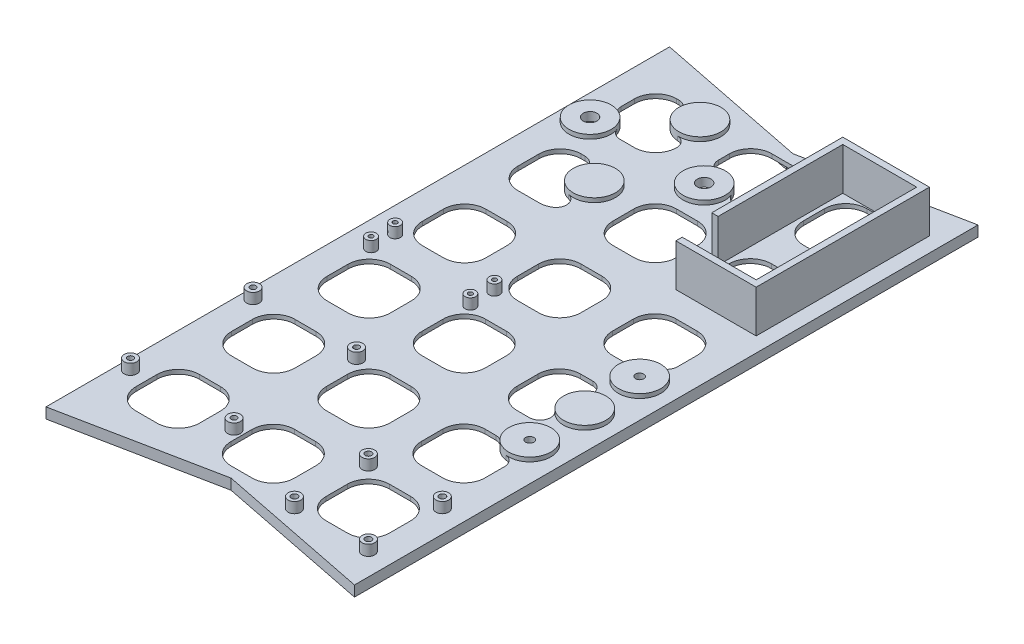
SolidWorks part; units mm, degrees
ref_plane "Front Plane" through (0, 0, 0) normal (0, 0, 1) x (1, 0, 0)
ref_plane "Top Plane" through (0, 0, 0) normal (0, 1, 0) x (1, 0, 0)
ref_plane "Right Plane" through (0, 0, 0) normal (1, 0, 0) x (0, 0, -1)
ref_axis "X" through (-88.99, 0, 0) along (1, 0, 0)
ref_axis "Y" through (0, 55, 0) along (0, -1, 0)
ref_axis "Z" through (0, 0, -88.99) along (0, 0, 1)
sketch "Sketch1" plane through (0, 0, 0) normal (0, 1, 0) x (1, 0, 0)
  line L0 (-75, 150) -> (0, 135) construction
  line L1 (-75, 150) -> (75, 150) construction
  line L2 (-75, 150) -> (-75, -150) construction
  line L3 (-75, -150) -> (75, -150) construction
  line L4 (75, 150) -> (75, -150) construction
  line L5 (-75, 150) -> (75, -150) construction
  line L6 (-75, -150) -> (75, 150) construction
  line L7 (0, 135) -> (75, 150) construction
  line L8 (-75, 0) -> (75, 0) construction
  line L9 (-75, -150) -> (0, -135) construction
  line L10 (0, -135) -> (75, -150) construction
  line L11 (-73, 147.5604) -> (-73, -147.5604)
  line L12 (-73, -147.5604) -> (0, -132.9604)
  line L13 (0, -132.9604) -> (73, -147.5604)
  line L14 (73, 147.5604) -> (73, -147.5604)
  line L15 (0, 132.9604) -> (73, 147.5604)
  line L16 (-73, 147.5604) -> (0, 132.9604)
  point P0 (0, 0)
  dimension "D1" = 300
  dimension "D2" = 150
  dimension "D3" = 15
  dimension "D4" = 2
extrude "Boss-Extrude1" add sketch "Sketch1" along normal blind 2
sketch "Sketch2" plane through (0, 2, 0) normal (0, 1, 0) x (1, 0, 0)
  line L0 (-73, 147.5604) -> (-73, -147.5604) construction
  line L1 (-50, -127.9604) -> (-40, -127.9604)
  line L2 (-60, -117.9604) -> (-60, -107.9604)
  line L3 (-50, -97.9604) -> (-40, -97.9604)
  line L4 (-30, -117.9604) -> (-30, -107.9604)
  line L5 (-15, -117.9604) -> (-15, -107.9604)
  line L6 (-5, -127.9604) -> (5, -127.9604)
  line L7 (15, -117.9604) -> (15, -107.9604)
  line L8 (-5, -97.9604) -> (5, -97.9604)
  line L9 (30, -117.9604) -> (30, -107.9604)
  line L10 (40, -127.9604) -> (50, -127.9604)
  line L11 (60, -117.9604) -> (60, -107.9604)
  line L12 (40, -97.9604) -> (50, -97.9604)
  line L73 (-60, -72.7762) -> (-60, -62.7762)
  line L74 (-50, -82.7762) -> (-40, -82.7762)
  line L75 (-30, -72.7762) -> (-30, -62.7762)
  line L76 (-50, -52.7762) -> (-40, -52.7762)
  line L77 (-15, -72.7762) -> (-15, -62.7762)
  line L78 (-5, -52.7762) -> (5, -52.7762)
  line L79 (15, -72.7762) -> (15, -62.7762)
  line L80 (-5, -82.7762) -> (5, -82.7762)
  line L81 (30, -72.7762) -> (30, -62.7762)
  line L82 (40, -52.7762) -> (50, -52.7762)
  line L83 (60, -72.7762) -> (60, -62.7762)
  line L84 (40, -82.7762) -> (50, -82.7762)
  line L85 (-60, -27.5921) -> (-60, -17.5921)
  line L86 (-50, -37.5921) -> (-40, -37.5921)
  line L87 (-30, -27.5921) -> (-30, -17.5921)
  line L88 (-50, -7.5921) -> (-40, -7.5921)
  line L89 (-15, -27.5921) -> (-15, -17.5921)
  line L90 (-5, -7.5921) -> (5, -7.5921)
  line L91 (15, -27.5921) -> (15, -17.5921)
  line L92 (-5, -37.5921) -> (5, -37.5921)
  line L93 (30, -27.5921) -> (30, -17.5921)
  line L94 (40, -7.5921) -> (50, -7.5921)
  line L95 (60, -27.5921) -> (60, -17.5921)
  line L96 (40, -37.5921) -> (50, -37.5921)
  line L97 (-60, 17.5921) -> (-60, 27.5921)
  line L98 (-50, 7.5921) -> (-40, 7.5921)
  line L99 (-30, 17.5921) -> (-30, 27.5921)
  line L100 (-50, 37.5921) -> (-40, 37.5921)
  line L101 (-15, 17.5921) -> (-15, 27.5921)
  line L102 (-5, 37.5921) -> (5, 37.5921)
  line L103 (15, 17.5921) -> (15, 27.5921)
  line L104 (-5, 7.5921) -> (5, 7.5921)
  line L105 (30, 17.5921) -> (30, 27.5921)
  line L106 (40, 37.5921) -> (50, 37.5921)
  line L107 (60, 17.5921) -> (60, 27.5921)
  line L108 (40, 7.5921) -> (50, 7.5921)
  line L109 (-60, 62.7762) -> (-60, 72.7762)
  line L110 (-50, 52.7762) -> (-40, 52.7762)
  line L111 (-30, 62.7762) -> (-30, 72.7762)
  line L112 (-50, 82.7762) -> (-40, 82.7762)
  line L113 (-15, 62.7762) -> (-15, 72.7762)
  line L114 (-5, 82.7762) -> (5, 82.7762)
  line L115 (15, 62.7762) -> (15, 72.7762)
  line L116 (-5, 52.7762) -> (5, 52.7762)
  line L117 (30, 62.7762) -> (30, 72.7762)
  line L118 (40, 82.7762) -> (50, 82.7762)
  line L119 (60, 62.7762) -> (60, 72.7762)
  line L120 (40, 52.7762) -> (50, 52.7762)
  line L121 (-60, 107.9604) -> (-60, 117.9604)
  line L122 (-50, 97.9604) -> (-40, 97.9604)
  line L123 (-30, 107.9604) -> (-30, 117.9604)
  line L124 (-50, 127.9604) -> (-40, 127.9604)
  line L125 (-15, 107.9604) -> (-15, 117.9604)
  line L126 (-5, 127.9604) -> (5, 127.9604)
  line L127 (15, 107.9604) -> (15, 117.9604)
  line L128 (-5, 97.9604) -> (5, 97.9604)
  line L129 (30, 107.9604) -> (30, 117.9604)
  line L130 (40, 127.9604) -> (50, 127.9604)
  line L131 (60, 107.9604) -> (60, 117.9604)
  line L132 (40, 97.9604) -> (50, 97.9604)
  arc A0 (-60, -117.9604) -> (-50, -127.9604) centre (-50, -117.9604) ccw
  arc A1 (-40, -127.9604) -> (-30, -117.9604) centre (-40, -117.9604) ccw
  arc A2 (-30, -107.9604) -> (-40, -97.9604) centre (-40, -107.9604) ccw
  arc A3 (-50, -97.9604) -> (-60, -107.9604) centre (-50, -107.9604) ccw
  arc A4 (60, -107.9604) -> (50, -97.9604) centre (50, -107.9604) ccw
  arc A5 (50, -127.9604) -> (60, -117.9604) centre (50, -117.9604) ccw
  arc A6 (40, -127.9604) -> (30, -117.9604) centre (40, -117.9604) cw
  arc A7 (30, -107.9604) -> (40, -97.9604) centre (40, -107.9604) cw
  arc A8 (-15, -107.9604) -> (-5, -97.9604) centre (-5, -107.9604) cw
  arc A9 (-15, -117.9604) -> (-5, -127.9604) centre (-5, -117.9604) ccw
  arc A10 (15, -117.9604) -> (5, -127.9604) centre (5, -117.9604) cw
  arc A11 (15, -107.9604) -> (5, -97.9604) centre (5, -107.9604) ccw
  arc A12 (-50, -52.7762) -> (-60, -62.7762) centre (-50, -62.7762) ccw
  arc A13 (-60, -72.7762) -> (-50, -82.7762) centre (-50, -72.7762) ccw
  arc A14 (-40, -82.7762) -> (-30, -72.7762) centre (-40, -72.7762) ccw
  arc A15 (-30, -62.7762) -> (-40, -52.7762) centre (-40, -62.7762) ccw
  arc A16 (-15, -72.7762) -> (-5, -82.7762) centre (-5, -72.7762) ccw
  arc A17 (-15, -62.7762) -> (-5, -52.7762) centre (-5, -62.7762) cw
  arc A18 (15, -62.7762) -> (5, -52.7762) centre (5, -62.7762) ccw
  arc A19 (15, -72.7762) -> (5, -82.7762) centre (5, -72.7762) cw
  arc A20 (30, -62.7762) -> (40, -52.7762) centre (40, -62.7762) cw
  arc A21 (40, -82.7762) -> (30, -72.7762) centre (40, -72.7762) cw
  arc A22 (60, -62.7762) -> (50, -52.7762) centre (50, -62.7762) ccw
  arc A23 (50, -82.7762) -> (60, -72.7762) centre (50, -72.7762) ccw
  arc A24 (-50, -7.5921) -> (-60, -17.5921) centre (-50, -17.5921) ccw
  arc A25 (-60, -27.5921) -> (-50, -37.5921) centre (-50, -27.5921) ccw
  arc A26 (-40, -37.5921) -> (-30, -27.5921) centre (-40, -27.5921) ccw
  arc A27 (-30, -17.5921) -> (-40, -7.5921) centre (-40, -17.5921) ccw
  arc A28 (-15, -27.5921) -> (-5, -37.5921) centre (-5, -27.5921) ccw
  arc A29 (-15, -17.5921) -> (-5, -7.5921) centre (-5, -17.5921) cw
  arc A30 (15, -17.5921) -> (5, -7.5921) centre (5, -17.5921) ccw
  arc A31 (15, -27.5921) -> (5, -37.5921) centre (5, -27.5921) cw
  arc A32 (30, -17.5921) -> (40, -7.5921) centre (40, -17.5921) cw
  arc A33 (40, -37.5921) -> (30, -27.5921) centre (40, -27.5921) cw
  arc A34 (60, -17.5921) -> (50, -7.5921) centre (50, -17.5921) ccw
  arc A35 (50, -37.5921) -> (60, -27.5921) centre (50, -27.5921) ccw
  arc A36 (-50, 37.5921) -> (-60, 27.5921) centre (-50, 27.5921) ccw
  arc A37 (-60, 17.5921) -> (-50, 7.5921) centre (-50, 17.5921) ccw
  arc A38 (-40, 7.5921) -> (-30, 17.5921) centre (-40, 17.5921) ccw
  arc A39 (-30, 27.5921) -> (-40, 37.5921) centre (-40, 27.5921) ccw
  arc A40 (-15, 17.5921) -> (-5, 7.5921) centre (-5, 17.5921) ccw
  arc A41 (-15, 27.5921) -> (-5, 37.5921) centre (-5, 27.5921) cw
  arc A42 (15, 27.5921) -> (5, 37.5921) centre (5, 27.5921) ccw
  arc A43 (15, 17.5921) -> (5, 7.5921) centre (5, 17.5921) cw
  arc A44 (30, 27.5921) -> (40, 37.5921) centre (40, 27.5921) cw
  arc A45 (40, 7.5921) -> (30, 17.5921) centre (40, 17.5921) cw
  arc A46 (60, 27.5921) -> (50, 37.5921) centre (50, 27.5921) ccw
  arc A47 (50, 7.5921) -> (60, 17.5921) centre (50, 17.5921) ccw
  arc A48 (-50, 82.7762) -> (-60, 72.7762) centre (-50, 72.7762) ccw
  arc A49 (-60, 62.7762) -> (-50, 52.7762) centre (-50, 62.7762) ccw
  arc A50 (-40, 52.7762) -> (-30, 62.7762) centre (-40, 62.7762) ccw
  arc A51 (-30, 72.7762) -> (-40, 82.7762) centre (-40, 72.7762) ccw
  arc A52 (-15, 62.7762) -> (-5, 52.7762) centre (-5, 62.7762) ccw
  arc A53 (-15, 72.7762) -> (-5, 82.7762) centre (-5, 72.7762) cw
  arc A54 (15, 72.7762) -> (5, 82.7762) centre (5, 72.7762) ccw
  arc A55 (15, 62.7762) -> (5, 52.7762) centre (5, 62.7762) cw
  arc A56 (30, 72.7762) -> (40, 82.7762) centre (40, 72.7762) cw
  arc A57 (40, 52.7762) -> (30, 62.7762) centre (40, 62.7762) cw
  arc A58 (60, 72.7762) -> (50, 82.7762) centre (50, 72.7762) ccw
  arc A59 (50, 52.7762) -> (60, 62.7762) centre (50, 62.7762) ccw
  arc A60 (-50, 127.9604) -> (-60, 117.9604) centre (-50, 117.9604) ccw
  arc A61 (-60, 107.9604) -> (-50, 97.9604) centre (-50, 107.9604) ccw
  arc A62 (-40, 97.9604) -> (-30, 107.9604) centre (-40, 107.9604) ccw
  arc A63 (-30, 117.9604) -> (-40, 127.9604) centre (-40, 117.9604) ccw
  arc A64 (-15, 107.9604) -> (-5, 97.9604) centre (-5, 107.9604) ccw
  arc A65 (-15, 117.9604) -> (-5, 127.9604) centre (-5, 117.9604) cw
  arc A66 (15, 117.9604) -> (5, 127.9604) centre (5, 117.9604) ccw
  arc A67 (15, 107.9604) -> (5, 97.9604) centre (5, 107.9604) cw
  arc A68 (30, 117.9604) -> (40, 127.9604) centre (40, 117.9604) cw
  arc A69 (40, 97.9604) -> (30, 107.9604) centre (40, 107.9604) cw
  arc A70 (60, 117.9604) -> (50, 127.9604) centre (50, 117.9604) ccw
  arc A71 (50, 97.9604) -> (60, 107.9604) centre (50, 107.9604) ccw
  point P81 (-30, -127.9604)
  point P84 (-30, -97.9604)
  point P87 (-60, -97.9604)
  dimension "D9" = 10
  dimension "D7" = 10
  dimension "D1" = 30
  dimension "D2" = 30
  dimension "D3" = 13
  dimension "D4" = 5
  dimension "D6" = 15
  dimension "D8" = 6
  dimension "D10" = 5
  dimension "D5" = 3
extrude "Cut-Extrude1" cut sketch "Sketch2" against normal through all
sketch "Sketch3" plane through (0, 2, 0) normal (0, 1, 0) x (1, 0, 0)
  line L1 (-73, 147.5604) -> (-73, -147.5604) construction
  circle A0 centre (-68, -54.5604) radius 3
  circle A1 centre (-19, -54.5604) radius 3
  circle A2 centre (-68, -112.5604) radius 3
  circle A3 centre (-19, -112.5604) radius 3
  point P8 (66.2833, 107.9604)
  dimension "D1" = 6
  dimension "D2" = 49
  dimension "D3" = 58
  dimension "D4" = 5
  dimension "D5" = 35
extrude "Boss-Extrude2" add sketch "Sketch3" along normal blind 5 and the other way through all
sketch "Sketch4" plane through (0, 7, 0) normal (0, 1, 0) x (1, 0, 0)
  circle A1 centre (-19, -112.5604) radius 1.35
  circle A2 centre (-68, -112.5604) radius 1.35
  circle A3 centre (-68, -54.5604) radius 1.35
  circle A4 centre (-19, -54.5604) radius 1.35
  dimension "D1" = 2.7
extrude "Cut-Extrude2" cut sketch "Sketch4" against normal through all
sketch "Sketch5" plane through (0, 2, 0) normal (0, 1, 0) x (1, 0, 0)
  line L0 (30, -112.9604) -> (60, -112.9604) construction
  line L1 (30, -107.9604) -> (30, -117.9604) construction
  line L2 (60, -117.9604) -> (60, -107.9604) construction
  circle A0 centre (27.5, -95.4604) radius 3
  circle A2 centre (62.5, -95.4604) radius 3
  circle A4 centre (62.5, -130.4604) radius 3
  circle A6 centre (27.5, -130.4604) radius 3
  circle A9 centre (45, -112.9604) radius 24.7487 construction
  point P14 (61.6729, -131.1014)
  point P15 (34.8916, -135.4406)
  point P16 (0, 0)
  dimension "D2" = 6
  dimension "D3" = 35
  dimension "D4" = 35
extrude "Boss-Extrude3" add sketch "Sketch5" along normal blind 5
sketch "Sketch6" plane through (0, 7, 0) normal (0, 1, 0) x (1, 0, 0)
  circle A0 centre (27.5, -95.4604) radius 1.5
  circle A1 centre (62.5, -95.4604) radius 1.5
  circle A2 centre (62.5, -130.4604) radius 1.5
  circle A3 centre (27.5, -130.4604) radius 1.5
  dimension "D1" = 3
extrude "Cut-Extrude3" cut sketch "Sketch6" against normal through all
sketch "Sketch7" plane through (0, 2, 0) normal (0, 1, 0) x (1, 0, 0)
  line L0 (73, -147.5604) -> (73, 147.5604) construction
  line L1 (30, -22.5921) -> (73, -22.5921) construction
  line L2 (30, -17.5921) -> (30, -27.5921) construction
  line L3 (57, 3.4079) -> (57, -48.5921) construction
  circle A0 centre (57, -48.5921) radius 10
  circle A1 centre (57, 3.4079) radius 10
  circle A2 centre (57, -22.5921) radius 10
  point P6 (51.5, -22.5921)
  point P13 (57, -22.5921)
  dimension "D1" = 20
  dimension "D2" = 16
  dimension "D3" = 52
extrude "Boss-Extrude4" add sketch "Sketch7" along normal blind 2 and the other way through all
sketch "Sketch8" plane through (0, 4, 0) normal (0, 1, 0) x (1, 0, 0)
  circle A0 centre (57, 3.4079) radius 1.95
  circle A1 centre (57, -48.5921) radius 1.95
  dimension "D1" = 3.9
extrude "Cut-Extrude4" cut sketch "Sketch8" against normal through all
sketch "Sketch9" plane through (0, 2, 0) normal (0, 1, 0) x (1, 0, 0)
  line L0 (73, 0) -> (-73, 0) construction
  line L1 (73, -147.5604) -> (73, 147.5604) construction
  line L2 (-73, 147.5604) -> (-73, -147.5604) construction
  line L3 (-61, 5.7) -> (-61, -5.7) construction
  circle A0 centre (-61, 5.7) radius 2.5
  circle A1 centre (-61, -5.7) radius 2.5
  circle A2 centre (-14, -5.7) radius 2.5
  circle A3 centre (-14, 5.7) radius 2.5
  point P14 (-61, 0)
  point P16 (-61.3065, 14.1633)
  point P17 (-14.4073, -5.7)
  dimension "D1" = 5
  dimension "D4" = 12
  dimension "D2" = 11.4
  dimension "D3" = 47
extrude "Boss-Extrude5" add sketch "Sketch9" along normal blind 5
sketch "Sketch10" plane through (0, 7, 0) normal (0, 1, 0) x (1, 0, 0)
  circle A0 centre (-14, 5.7) radius 1.05
  circle A1 centre (-14, -5.7) radius 1.05
  circle A2 centre (-61, -5.7) radius 1.05
  circle A3 centre (-61, 5.7) radius 1.05
  dimension "D1" = 2.1
extrude "Cut-Extrude5" cut sketch "Sketch10" against normal through all
sketch "Sketch11" plane through (0, 2, 0) normal (0, 1, 0) x (1, 0, 0)
  line L0 (-73, 147.5604) -> (-73, -147.5604) construction
  line L1 (-34, 122.9604) -> (-34, 72.9604) construction
  line L2 (-61, 97.9604) -> (-7, 97.9604) construction
  circle A3 centre (-7, 97.9604) radius 10
  circle A4 centre (-61, 97.9604) radius 10
  circle A5 centre (-34, 122.9604) radius 10
  circle A6 centre (-34, 72.9604) radius 10
  point P11 (-34, 97.9604)
  dimension "D1" = 20
  dimension "D2" = 54
  dimension "D3" = 35
  dimension "D4" = 12
  dimension "D5" = 50
extrude "Boss-Extrude6" add sketch "Sketch11" along normal blind 2 and the other way through all
sketch "Sketch12" plane through (0, 4, 0) normal (0, 1, 0) x (1, 0, 0)
  circle A0 centre (-61, 97.9604) radius 3.25
  circle A1 centre (-7, 97.9604) radius 3.25
  dimension "D1" = 6.5
extrude "Cut-Extrude6" cut sketch "Sketch12" against normal through all
sketch "Sketch13" plane through (0, 2, 0) normal (0, 1, 0) x (1, 0, 0)
  line L0 (28, 49.5604) -> (66, 49.5604)
  line L1 (66, 49.5604) -> (66, 131.5604)
  line L2 (66, 131.5604) -> (25, 131.5604)
  line L3 (25, 131.5604) -> (25, 69.5604)
  line L4 (25, 69.5604) -> (28, 69.5604)
  line L5 (28, 69.5604) -> (28, 128.5604)
  line L6 (28, 128.5604) -> (63, 128.5604)
  line L7 (63, 128.5604) -> (63, 52.5604)
  line L8 (63, 52.5604) -> (28, 52.5604)
  line L9 (28, 52.5604) -> (28, 49.5604)
  line L10 (73, -147.5604) -> (73, 147.5604) construction
  dimension "D1" = 62
  dimension "D2" = 3
  dimension "D3" = 3
  dimension "D4" = 3
  dimension "D5" = 3
  dimension "D6" = 35
  dimension "D7" = 76
  dimension "D8" = 16
  dimension "D9" = 7
extrude "Boss-Extrude7" add sketch "Sketch13" along normal blind 20 and the other way through all
fillet "Fillet2" radius 5 14 edges at (58.9879, 1, -13.2083) (47.9174, 1, -7.5921) (47.9174, 1, 52.7762) (58.9879, 1, 58.3925) (58.7473, 1, 32.4382) (58.7473, 1, 12.7459) (-30, 1, -63.7952) (-37.2926, 1, -82.4028) (-14.4353, 1, -104.6474) (3, 1, -97.9604) (-59.9999, 1, -107.9103) (-51.0001, 1, -98.0105) (-42.6603, 1, -127.9604) (-30, 1, -113.7952)
sketch "Sketch15" plane through (0, 0, 0) normal (0, -1, 0) x (1, 0, 0)
  line L0 (0, 132.9604) -> (73, 147.5604) construction
  line L1 (-73, 147.5604) -> (0, 132.9604) construction
  line L2 (73, 147.5604) -> (73, -147.5604) construction
  line L3 (73, -147.5604) -> (0, -132.9604) construction
  line L4 (0, -132.9604) -> (-73, -147.5604) construction
  line L5 (-73, -147.5604) -> (-73, 147.5604) construction
  line L6 (0, 132.9604) -> (73, 147.5604)
  line L7 (-73, 147.5604) -> (0, 132.9604)
  line L8 (73, 147.5604) -> (73, -147.5604)
  line L9 (73, -147.5604) -> (0, -132.9604)
  line L10 (0, -132.9604) -> (-73, -147.5604)
  line L11 (-73, -147.5604) -> (-73, 147.5604)
  line L12 (0, 129.901) -> (70, 143.901)
  line L13 (70, 143.901) -> (70, -143.901)
  line L14 (70, -143.901) -> (0, -129.901)
  line L15 (0, -129.901) -> (-70, -143.901)
  line L16 (-70, -143.901) -> (-70, 143.901)
  line L17 (-70, 143.901) -> (0, 129.901)
  dimension "D1" = 3
extrude "Boss-Extrude9" add sketch "Sketch15" along normal blind 3
